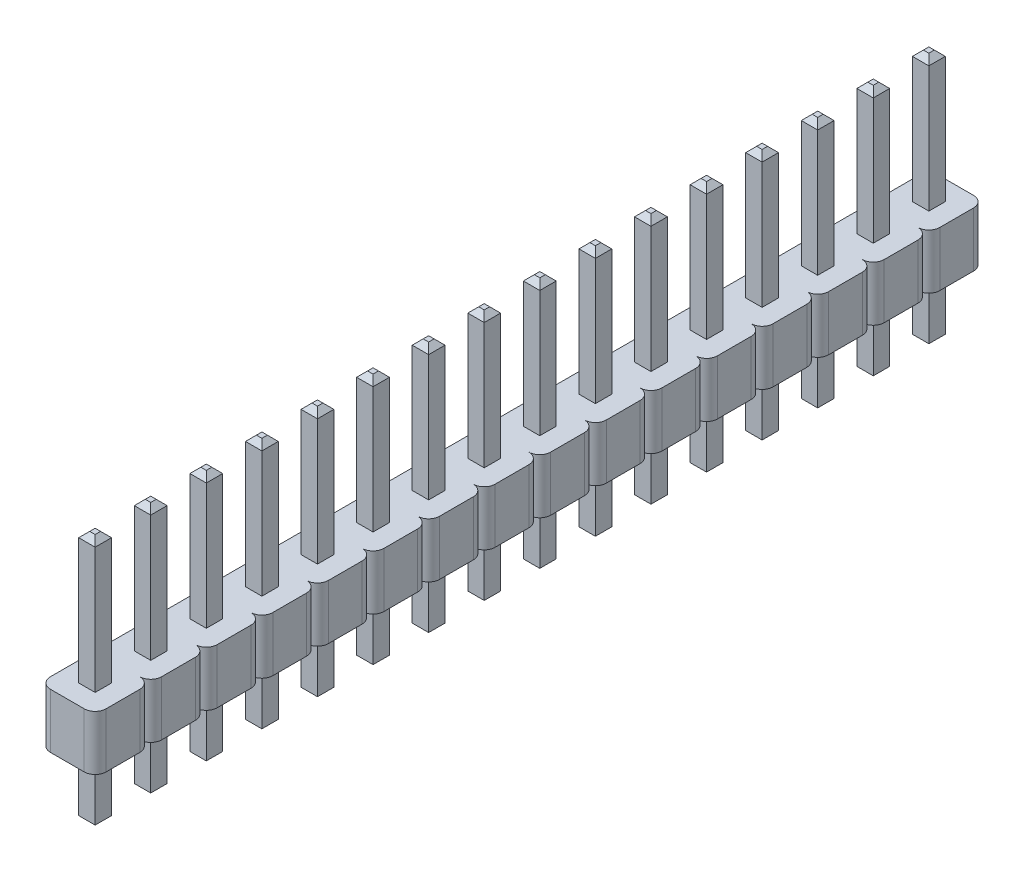
SolidWorks part; units mm, degrees
ref_plane "Front Plane" through (0, 0, 0) normal (0, 0, 1) x (1, 0, 0)
ref_plane "Top Plane" through (0, 0, 0) normal (0, 1, 0) x (1, 0, 0)
ref_plane "Right Plane" through (0, 0, 0) normal (1, 0, 0) x (0, 0, -1)
ref_plane "Plane1" through (0, 0, 0) normal (0, 1, 0) x (-1, 0, 0)
sketch "Sketch1" plane through (0, 0, 0) normal (0, 1, 0) x (-1, 0, 0)
  line L0 (-0.77, 1.27) -> (0.77, 1.27)
  line L1 (1.27, 0.77) -> (1.27, -0.77)
  line L2 (0.77, -1.27) -> (-0.77, -1.27)
  line L3 (-1.27, -0.77) -> (-1.27, 0.77)
  line L4 (-0.77, 0.77) -> (0.77, -0.77) construction
  arc A0 (1.27, 0.77) -> (0.77, 1.27) centre (0.77, 0.77) ccw
  arc A1 (0.77, -1.27) -> (1.27, -0.77) centre (0.77, -0.77) ccw
  arc A2 (-1.27, -0.77) -> (-0.77, -1.27) centre (-0.77, -0.77) ccw
  arc A3 (-0.77, 1.27) -> (-1.27, 0.77) centre (-0.77, 0.77) ccw
  dimension "D3" = 0.5
  dimension "D2" = 2.54
extrude "Boss-Extrude1" add sketch "Sketch1" along normal blind 2.5
ref_plane "Plane2" through (0.77, 0, 1.27) normal (-1, 0, 0) x (0, 0, 1)
ref_plane "Plane3" through (0.77, 0, 1.27) normal (0, -1, 0) x (0, 0, 1)
ref_axis "Axis1" through (0.77, 0, -79.63) along (0, 0, 1)
pattern_linear "LPattern1" count 16 spacing 2.54 along (0, 0, 1) of "Boss-Extrude1"
ref_plane "Plane4" through (0, 0, 0) normal (0, 1, 0) x (-1, 0, 0)
sketch "Sketch2" plane through (0, 0, 0) normal (0, 1, 0) x (-1, 0, 0)
  line L0 (-0.375, 0.375) -> (0.375, 0.375)
  line L1 (0.375, 0.375) -> (0.375, -0.375)
  line L2 (0.375, -0.375) -> (-0.375, -0.375)
  line L3 (-0.375, -0.375) -> (-0.375, 0.375)
  line L4 (-0.375, 0.375) -> (0.375, -0.375) construction
  dimension "D1" = 0.75
extrude "Boss-Extrude2" add sketch "Sketch2" along normal blind 8.5 and the other way blind 3
ref_plane "Plane5" through (0.3725, 0, 0.3725) normal (-1, 0, 0) x (0, 0, 1)
ref_plane "Plane6" through (0.3725, 0, 0.3725) normal (0, -1, 0) x (0, 0, 1)
ref_axis "Axis2" through (0.3725, 0, -80.5275) along (0, 0, 1)
chamfer "Chamfer1" distance 0.25 angle 45 8 edges at (0, -3, 0.375) (-0.375, -3, 0) (0.375, -3, 0) (0, -3, -0.375) (0, 8.5, 0.375) (-0.375, 8.5, 0) (0, 8.5, -0.375) (0.375, 8.5, 0)
pattern_linear "LPattern2" count 16 spacing 2.54 along (0, 0, 1) of "Boss-Extrude2", "Chamfer1"
ref_axis "Axis3" through (0, -3.575, 0) along (0, 1, 0)
